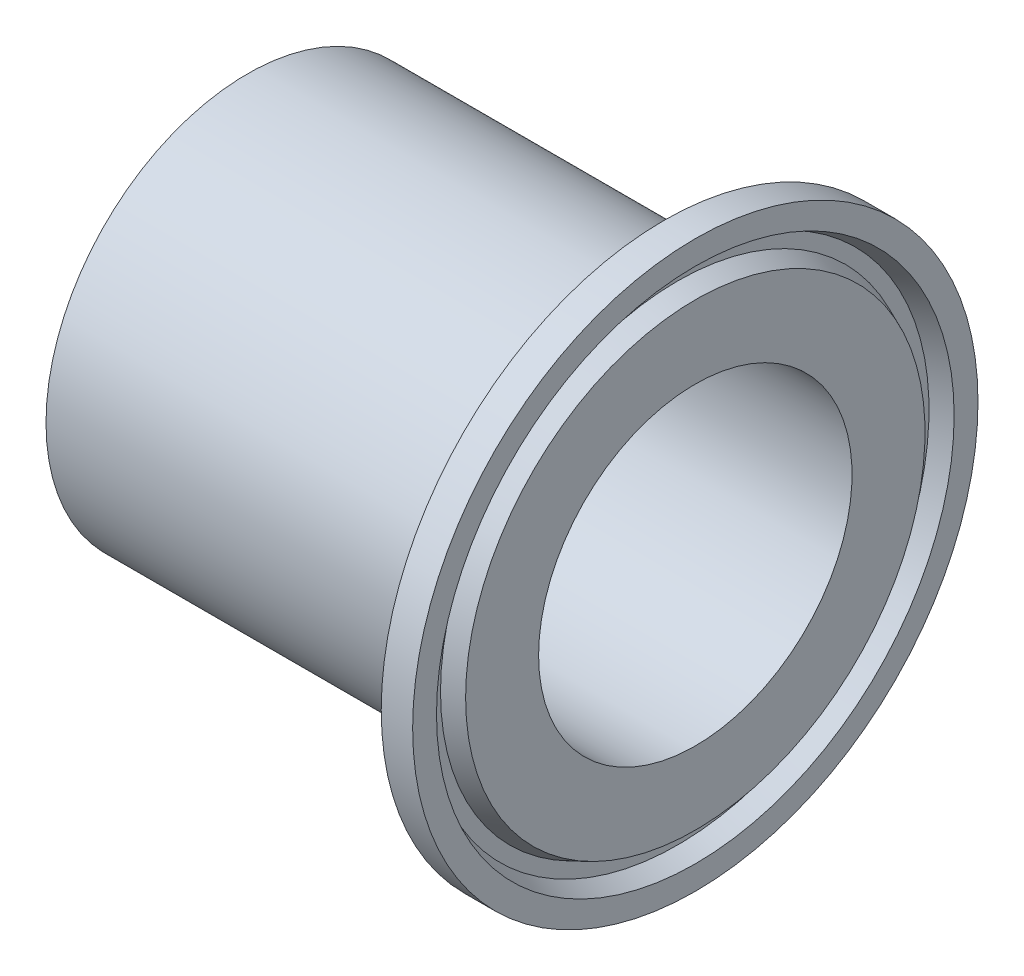
SolidWorks part; units mm, degrees
material "6061 Alloy"
ref_plane "Front Plane" through (0, 0, 0) normal (0, 0, 1) x (1, 0, 0)
ref_plane "Top Plane" through (0, 0, 0) normal (0, 1, 0) x (1, 0, 0)
ref_plane "Right Plane" through (0, 0, 0) normal (1, 0, 0) x (0, 0, -1)
sketch "Sketch1" plane through (0, 0, 0) normal (0, 0, 1) x (1, 0, 0)
  line L4 (34.5545, 18) -> (37.1933, 25.25)
  line L5 (37.1933, 25.25) -> (40, 25.25)
  line L6 (40, 25.25) -> (40, 23.1186)
  line L8 (0, 0) -> (52.6945, 0) construction
  line L9 (0, 11.0575) -> (0, 0) construction
  line L10 (40, 23.1186) -> (38.4252, 22.4501)
  line L11 (38.4252, 22.4501) -> (38.4252, 21.1871)
  line L12 (38.4252, 21.1871) -> (40, 20.5186)
  line L13 (38.4252, 21.8186) -> (40, 21.8186) construction
  line L14 (40, 20.5186) -> (40, 14)
  line L19 (35, 14) -> (0, 14)
  line L20 (34.5545, 18) -> (0, 18)
  line L21 (0, 14) -> (0, 18)
  line L22 (40, 14) -> (40, 12)
  line L23 (40, 12) -> (35, 12)
  line L24 (35, 12) -> (35, 14)
  line L25 (40, 14) -> (35, 14) construction
  circle A1 centre (40, 21.8186) radius 1.15 construction
  dimension "D14" = 2.3
  dimension "D1" = 20
  dimension "D2" = 25.25
  dimension "D3" = 2.8067
  dimension "D4" = 2
  dimension "D5" = 4
  dimension "D6" = 28
  dimension "D7" = 5
  dimension "D8" = 40
  dimension "D10" = 46
  dimension "D11" = 21.8186
  dimension "D12" = 1.5748
  dimension "D13" = 2.6
revolve "Revolve1" add sketch "Sketch1" angle 360 about L8
fillet "Fillet1" [suppressed] radius 1.1938
fillet "Fillet2" [suppressed] radius 0.7874
sketch "Sketch2" plane through (0, 0, 0) normal (0, 0, 1) x (1, 0, 0)
  line L0 (15, 0) -> (0, 0) construction
  line L1 (24, 6) -> (6, 6)
  line L2 (24, 6) -> (24, -6)
  line L3 (24, -6) -> (6, -6)
  line L4 (6, 6) -> (6, -6)
  line L5 (24, 6) -> (6, -6) construction
  line L6 (24, -6) -> (6, 6) construction
  point P0 (15, 0)
  dimension "D1" = 12
  dimension "D2" = 18
  dimension "D3" = 15
chamfer "Chamfer1" distance 2 angle 45 1 edges at (0, 0, 14)
ref_axis "Axis1" through (-2, 0, 0) along (1, 0, 0)
sketch "Sketch7" plane through (0, 0, 0) normal (-1, 0, 0) x (0, 0, 1)
  circle A0 centre (0, 0) radius 14
  circle A1 centre (0, 0) radius 14 construction
extrude "Cut-Extrude2" cut sketch "Sketch7" against normal through all
